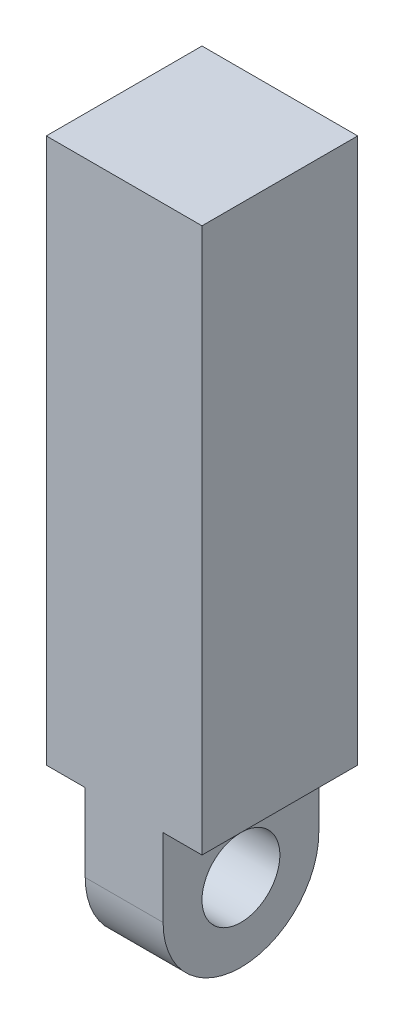
SolidWorks part; units mm, degrees
material "7075-T6 (SN)"
ref_plane "Front Plane" through (0, 0, 0) normal (0, 0, 1) x (1, 0, 0)
ref_plane "Top Plane" through (0, 0, 0) normal (0, 1, 0) x (1, 0, 0)
ref_plane "Right Plane" through (0, 0, 0) normal (1, 0, 0) x (0, 0, -1)
sketch "Sketch1" plane through (0, 0, 0) normal (0, 1, 0) x (1, 0, 0)
  line L1 (-50.8, -50.8) -> (50.8, -50.8)
  line L2 (-50.8, -50.8) -> (-50.8, 50.8)
  line L3 (-50.8, 50.8) -> (50.8, 50.8)
  line L4 (50.8, -50.8) -> (50.8, 50.8)
  line L5 (-50.8, -50.8) -> (50.8, 50.8) construction
  line L6 (-50.8, 50.8) -> (50.8, -50.8) construction
  point P0 (0, 0)
  dimension "D1" = 101.6
  dimension "D2" = 101.6
extrude "Boss-Extrude1" add sketch "Sketch1" along normal blind 457.2
sketch "Sketch2" plane through (0, 0, 50.8) normal (0, 0, 1) x (1, 0, 0)
  line L1 (-50.8, 0) -> (-25.4, 0)
  line L2 (-50.8, 0) -> (-50.8, 101.6)
  line L3 (-50.8, 101.6) -> (-25.4, 101.6)
  line L4 (-25.4, 0) -> (-25.4, 101.6)
  line L5 (50.8, 0) -> (25.4, 0)
  line L6 (50.8, 0) -> (50.8, 101.6)
  line L7 (50.8, 101.6) -> (25.4, 101.6)
  line L8 (25.4, 0) -> (25.4, 101.6)
  dimension "D1" = 101.6
  dimension "D2" = 25.4
  dimension "D3" = 25.4
  dimension "D4" = 101.6
extrude "Cut-Extrude1" cut sketch "Sketch2" against normal through all
fillet "Fillet1" radius 50.8 2 edges at (0, 0, -50.8) (0, 0, 50.8)
sketch "Sketch3" plane through (-25.4, 0, 0) normal (-1, 0, 0) x (0, 0, 1)
  circle A0 centre (0, 50.8) radius 25.4
  dimension "D2" = 50.8
  dimension "D1" = 50.8
extrude "Cut-Extrude2" cut sketch "Sketch3" against normal through all
